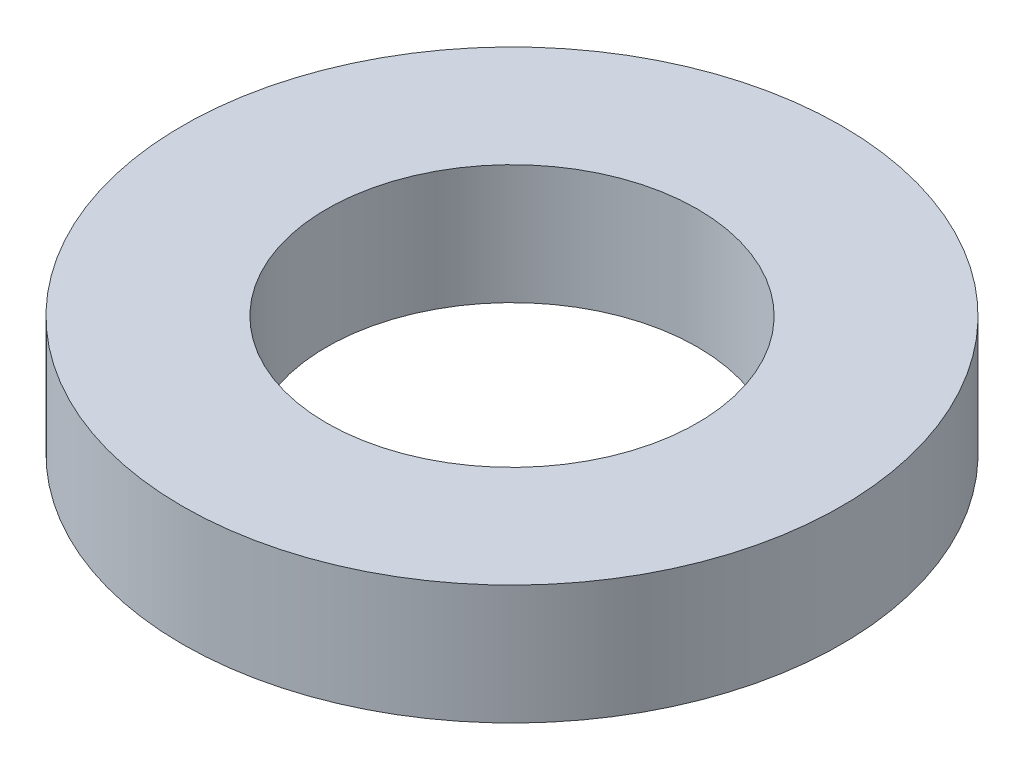
SolidWorks part; units mm, degrees
ref_plane "Front Plane" through (0, 0, 0) normal (0, 0, 1) x (1, 0, 0)
ref_plane "Top Plane" through (0, 0, 0) normal (0, 1, 0) x (1, 0, 0)
ref_plane "Right Plane" through (0, 0, 0) normal (1, 0, 0) x (0, 0, -1)
sketch "Sketch1" plane through (0, 0, 0) normal (0, 1, 0) x (1, 0, 0)
  circle A0 centre (0, 0) radius 80
  dimension "FLANGE_OD" = 160
extrude "Boss-Extrude1" add sketch "Sketch1" along normal blind 29
sketch "Sketch2" plane through (0, 0, 0) normal (0, 1, 0) x (1, 0, 0)
  circle A0 centre (0, 0) radius 45
  dimension "BORE_D" = 90
extrude "Cut-Extrude1" cut sketch "Sketch2" along normal through all
sketch "Sketch3" plane through (0, 29, 0) normal (0, 1, 0) x (1, 0, 0)
  circle A0 centre (0, 0) radius 28.595 construction
  circle A1 centre (-28.595, 0) radius 6.1184
  dimension "BOLT_D" = 12.2367
  dimension "BOLT_PCD" = 57.19
extrude "Cut-Extrude2" cut sketch "Sketch3" against normal blind 25.2582 rebuild error yes
pattern_circular "CirPattern1" count 3 over 360 rebuild error yes
